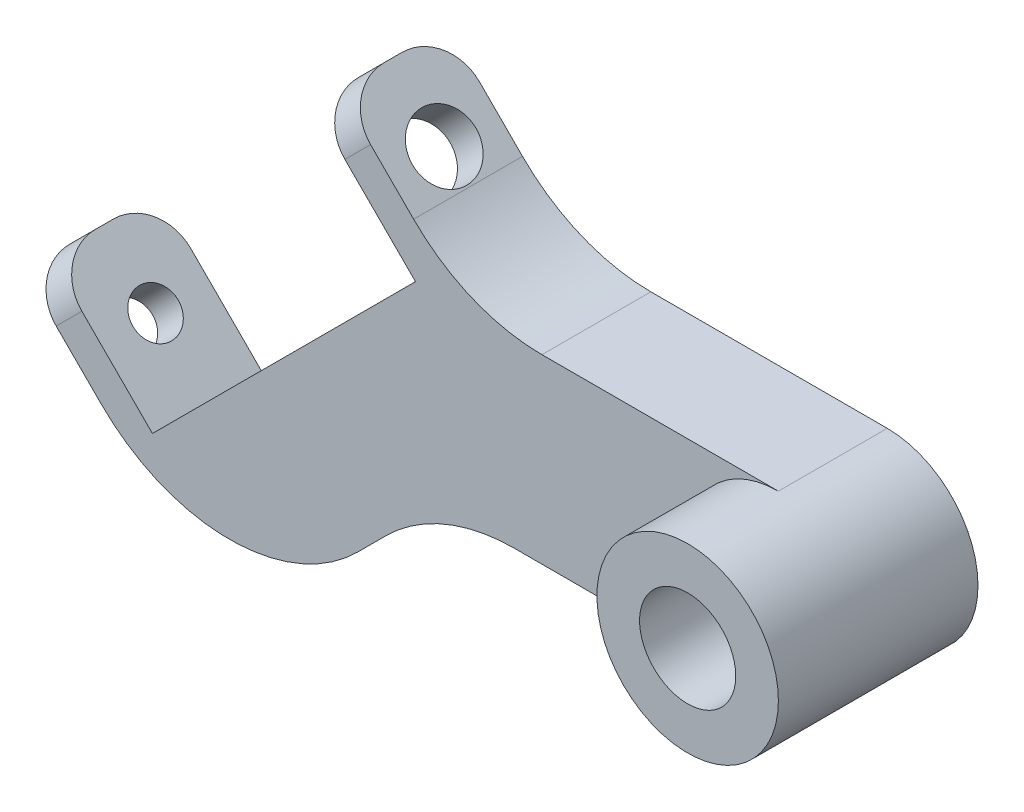
SolidWorks part; units mm, degrees
ref_plane "Piano frontale" through (0, 0, 0) normal (0, 0, 1) x (1, 0, 0)
ref_plane "Piano superiore" through (0, 0, 0) normal (0, 1, 0) x (1, 0, 0)
ref_plane "Piano destro" through (0, 0, 0) normal (1, 0, 0) x (0, 0, -1)
sketch "Schizzo1" plane through (0, 0, 0) normal (0, 0, 1) x (1, 0, 0)
  line L0 (0, 0) -> (-20, 0)
  line L1 (-20, 0) -> (-10, 10)
  line L2 (-10, 10) -> (10, 10)
  line L4 (10, 0) -> (0, 0)
  arc A0 (10, 0) -> (10, 10) centre (10, 5) ccw
  point P3 (0, 0)
  dimension "D6" = 10
  dimension "D1" = 20
  dimension "D2" = 10
  dimension "D3" = 10
  dimension "D4" = 0
  dimension "D5" = 20
extrude "Estrusione-Estrusione1" add sketch "Schizzo1" along normal blind 6 contours L2 A0 L4 L0 L1
sketch "Schizzo3" plane through (0, 0, 6) normal (0, 0, 1) x (1, 0, 0)
  arc A0 (10, 0) -> (10, 10) centre (10, 5) ccw construction
  arc A1 (10, 0) -> (10, 10) centre (10, 5) ccw construction
  circle A2 centre (10, 5) radius 5
  circle A3 centre (10, 5) radius 2.65
  dimension "D1" = 5.3
extrude "Estrusione-Estrusione3" add sketch "Schizzo3" along normal blind 5
sketch "Schizzo4" plane through (0, 0, 6) normal (0, 0, 1) x (1, 0, 0)
  line L0 (-10, 10) -> (-16.0795, 16.0795)
  line L1 (-20, 0) -> (-10, 10) construction
ref_plane "Piano1" through (0, 0, 0) normal (0.7071, 0.7071, 0) x (-0.7071, 0.7071, 0)
sketch "Schizzo5" plane through (0, 0, 0) normal (0.7071, 0.7071, 0) x (-0.7071, 0.7071, 0)
  line L0 (14.1421, 3) -> (18.1421, 3)
  line L1 (14.1421, 6) -> (14.1421, 0) construction
  circle A0 centre (18.1421, 3) radius 0.925
  dimension "D2" = 1.85
  dimension "D1" = 4
extrude "Estrusione-Estrusione4" add sketch "Schizzo5" against normal blind 20 separate body contours A0 region at (-12.8284, 12.8284, 2.1012)
sketch "Schizzo12" plane through (0, 0, 0) normal (0.7071, 0.7071, 0) x (-0.7071, 0.7071, 0)
  line L0 (14.1421, 0) -> (0, 0) construction
  line L1 (14.1421, 6) -> (22.1421, 6)
  line L2 (14.1421, 6) -> (14.1421, 0)
  line L3 (14.1421, 0) -> (22.1421, 0)
  line L4 (22.1421, 6) -> (22.1421, 0)
  dimension "D1" = 8
extrude "Estrusione-Estrusione6" add sketch "Schizzo12" along normal blind 2
sketch "Schizzo13" plane through (-10, 10, 0) normal (0.7071, -0.7071, 0) x (0, 0, -1)
  line L4 (-6, 0) -> (0, 0)
  line L5 (0, 0) -> (0, 2)
  line L6 (0, 2) -> (-6, 2)
  line L7 (-6, 2) -> (-6, 0)
  line L8 (-6, 0) -> (0, 0)
  line L9 (0, 0) -> (0, 2)
  line L10 (0, 2) -> (-6, 2)
  line L11 (-6, 2) -> (-6, 0)
  dimension "D1" = 0
extrude "Estrusione-Estrusione7" add sketch "Schizzo13" along normal blind 3
fillet "Raccordo2" radius 2.5 2 edges at (-14.9497, 16.364, 0) (-14.9497, 16.364, 6)
sketch "Schizzo14" plane through (1.4142, 1.4142, 0) normal (0.7071, 0.7071, 0) x (0, 0, -1)
  circle A0 centre (-3, 18.1421) radius 1.75
  circle A1 centre (-3, 18.1421) radius 0.925
  circle A2 centre (-3, 18.1421) radius 0.925
  dimension "D2" = 3.5
  dimension "D1" = 0
extrude "Taglio-Estrusione7" cut sketch "Schizzo14" against normal blind 25 contours A2 | A0 A2 | A2 | A0 region at (-11.4142, 14.2426, 4.7005) region at (-11.4142, 14.2426, 3)
sketch "Schizzo15" plane through (0, 0, 0) normal (-0.7071, -0.7071, 0) x (0, 0, 1)
  line L0 (0, 14.1421) -> (0, 19.6421) construction
  line L1 (6, 14.1421) -> (0, 14.1421)
  line L2 (6, 14.1421) -> (6, 6.1421)
  line L3 (6, 6.1421) -> (0, 6.1421)
  line L4 (0, 14.1421) -> (0, 6.1421)
  dimension "D1" = 8
extrude "Estrusione-Estrusione8" add sketch "Schizzo15" along normal blind 22.5
sketch "Schizzo16" plane through (-10, 10, 0) normal (-0.7071, 0.7071, 0) x (0, 0, 1)
  line L0 (0, -22.5) -> (0, 0) construction
  line L1 (6, -22.5) -> (0, -22.5)
  line L2 (6, -22.5) -> (6, -20.5)
  line L3 (6, -20.5) -> (0, -20.5)
  line L4 (0, -22.5) -> (0, -20.5)
  dimension "D1" = 2
extrude "Estrusione-Estrusione9" add sketch "Schizzo16" along normal up to vertex up to point (-15.6569, 15.6569, 2.5)
sketch "Schizzo17" plane through (-15.9099, -15.9099, 0) normal (-0.7071, -0.7071, 0) x (0, 0, 1)
  circle A0 centre (3, 18.1421) radius 1.75 construction
  circle A1 centre (3, 18.1421) radius 1.75
  circle A2 centre (3, 18.1421) radius 1.25
  dimension "D1" = 2.5
extrude "Taglio-Estrusione8" cut sketch "Schizzo17" against normal blind 25 contours A2
fillet "Raccordo3" radius 10 1 edges at (-20.253, -11.5668, 3)
fillet "Raccordo4" radius 10 1 edges at (-8.6863, 0, 3)
fillet "Raccordo5" radius 10 1 edges at (-7.1716, 10, 3)
fillet "Raccordo6" radius 2.5 2 edges at (-30.8597, 0.4541, 0) (-30.8597, 0.4541, 6)
sketch "Schizzo18" plane through (0, 0, 6) normal (0, 0, 1) x (1, 0, 0)
  circle A0 centre (10, 5) radius 1.75
  dimension "D1" = 3.5
extrude "Taglio-Estrusione9" cut sketch "Schizzo18" against normal through all
ref_axis "Assi1" through (-14.0659, 11.591, 3) along (0.7071, 0.7071, 0)
ref_axis "Assi2" through (-13.8891, 13.8891, 6) along (0.7071, -0.7071, 0)
ref_axis "Assi3" through (-10.1005, 12.9289, 6) along (0, 0, -1)
ref_point "Punto1"
ref_point "Punto2"
ref_axis "Assi4" through (10, 5, 11) along (0, 0, -1)
ref_axis "Assi5" through (-3.0294, 10, 6) along (1, 0, 0)
